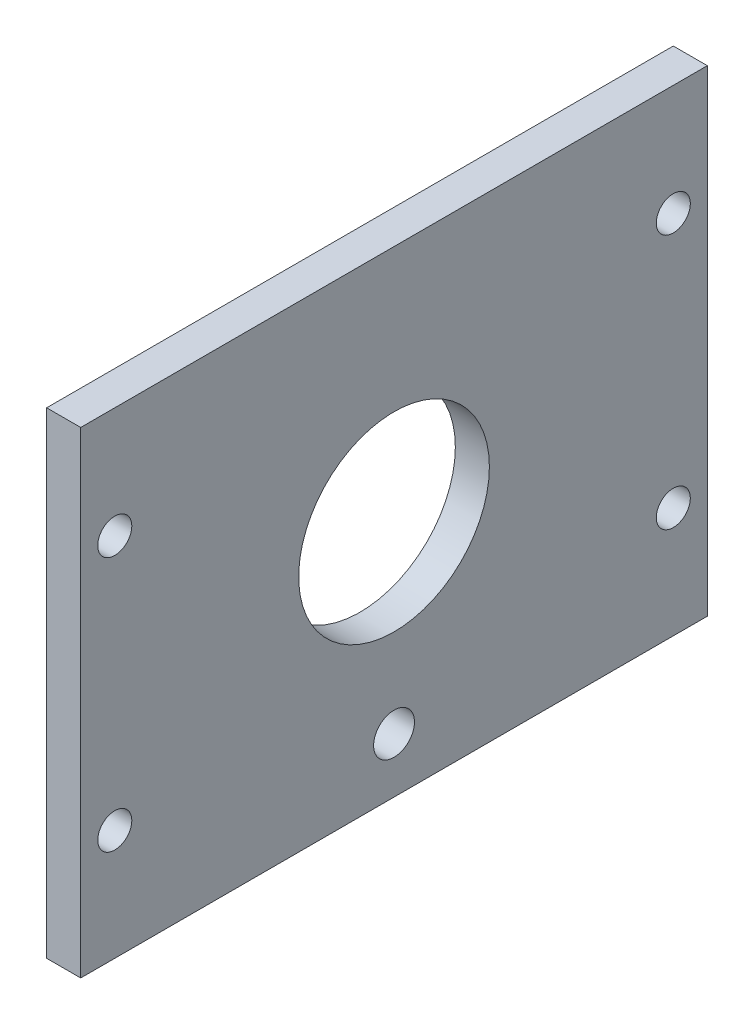
SolidWorks part; units mm, degrees
ref_plane "Front Plane" through (0, 0, 0) normal (0, 0, 1) x (1, 0, 0)
ref_plane "Top Plane" through (0, 0, 0) normal (0, 1, 0) x (1, 0, 0)
ref_plane "Right Plane" through (0, 0, 0) normal (1, 0, 0) x (0, 0, -1)
sketch "Sketch1" plane through (0, 0, 0) normal (1, 0, 0) x (0, 0, -1)
  line L0 (0, 0) -> (92, -70) construction
  line L1 (0, 0) -> (92, 0)
  line L2 (0, 0) -> (0, -70)
  line L3 (0, -70) -> (92, -70)
  line L4 (92, 0) -> (92, -70)
  line L5 (92, 0) -> (0, -70) construction
  line L6 (46, -35) -> (46, 0) construction
  line L7 (46, -17.5) -> (0, -17.5) construction
  circle A0 centre (46, -35) radius 14
  dimension "D3" = 28
  dimension "D1" = 70
  dimension "D2" = 92
extrude "Boss-Extrude1" add sketch "Sketch1" along normal blind 5
sketch "Sketch2" plane through (5, 0, 0) normal (1, 0, 0) x (0, 0, -1)
  line L0 (9.9892, 0) -> (9.9892, -70) construction
  line L1 (92, 0) -> (0, 0) construction
  line L2 (0, -70) -> (92, -70) construction
  line L3 (82.1061, 0) -> (82, -70) construction
  line L4 (82, 397) -> (82, -203) construction
  line L5 (9.9892, -35) -> (0, -35) construction
  line L6 (0, 0) -> (0, -70) construction
  line L7 (46, 0) -> (46, -70) construction
  circle A0 centre (5, -16.2724) radius 2.5
  circle A1 centre (5, -53.7276) radius 2.5
  circle A2 centre (87, -53.7276) radius 2.5
  circle A3 centre (87, -16.2724) radius 2.5
  dimension "D1" = 5
  dimension "D2" = 5
extrude "Cut-Extrude1" cut sketch "Sketch2" against normal through all both and the other way through all
sketch "Sketch3" plane through (5, 0, 0) normal (1, 0, 0) x (0, 0, -1)
  line L0 (46, -70) -> (46, -53.881) construction
  line L1 (0, -70) -> (92, -70) construction
  circle A0 centre (46, -61.9405) radius 3
  dimension "D1" = 6
extrude "Cut-Extrude2" cut sketch "Sketch3" against normal through all both and the other way through all
